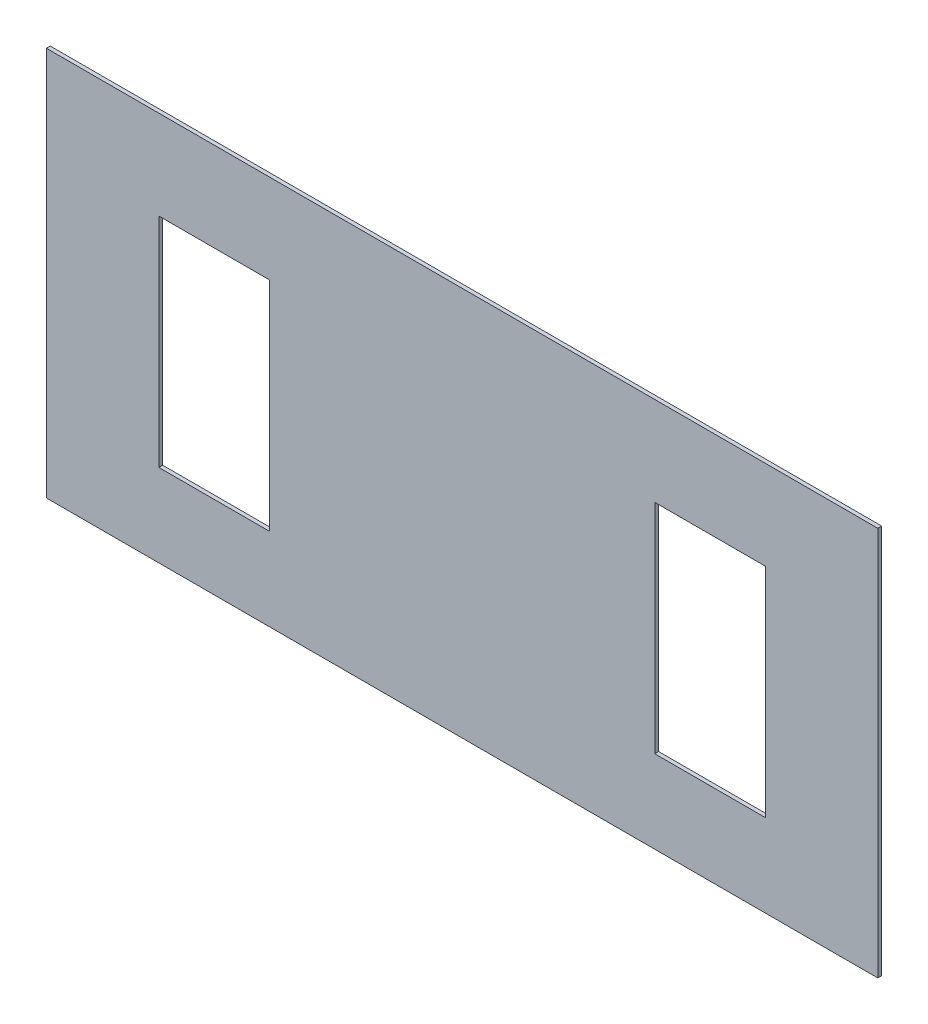
SolidWorks part; units mm, degrees
ref_plane "Front Plane" through (0, 0, 0) normal (0, 0, 1) x (1, 0, 0)
ref_plane "Top Plane" through (0, 0, 0) normal (0, 1, 0) x (1, 0, 0)
ref_plane "Right Plane" through (0, 0, 0) normal (1, 0, 0) x (0, 0, -1)
sketch "Sketch1" plane through (0, 0, 0) normal (0, 0, 1) x (1, 0, 0)
  line L0 (-11.525, -100) -> (-11.525, 103.337)
  line L1 (-11.525, 103.337) -> (422.475, 103.337)
  line L2 (422.475, 103.337) -> (422.475, -100)
  line L3 (422.475, -100) -> (-11.525, -100)
extrude "Boss-Extrude1" add sketch "Sketch1" along normal blind 2
sketch "Sketch2" plane through (0, 0, 2) normal (0, 0, 1) x (1, 0, 0)
  line L0 (205.475, -100) -> (205.475, 103.337) construction
  line L1 (104.8865, -56.8268) -> (47.1635, -56.8268)
  line L2 (104.8865, -56.8268) -> (104.8865, 56.8268)
  line L3 (104.8865, 56.8268) -> (47.1635, 56.8268)
  line L4 (47.1635, -56.8268) -> (47.1635, 56.8268)
  line L5 (104.8865, -56.8268) -> (47.1635, 56.8268) construction
  line L6 (104.8865, 56.8268) -> (47.1635, -56.8268) construction
  line L7 (-11.525, -100) -> (422.475, -100) construction
  line L8 (422.475, 103.337) -> (-11.525, 103.337) construction
  line L9 (306.0635, 56.8268) -> (363.7865, -56.8268) construction
  line L10 (306.0635, -56.8268) -> (363.7865, 56.8268) construction
  line L11 (363.7865, -56.8268) -> (363.7865, 56.8268)
  line L12 (306.0635, 56.8268) -> (363.7865, 56.8268)
  line L13 (306.0635, -56.8268) -> (306.0635, 56.8268)
  line L14 (306.0635, -56.8268) -> (363.7865, -56.8268)
  line L15 (76.025, 85.063) -> (76.025, -84.937) construction
  point P0 (76.025, 0)
  point P15 (334.925, 0)
  point P16 (0, 0)
extrude "Cut-Extrude1" cut sketch "Sketch2" against normal through all
